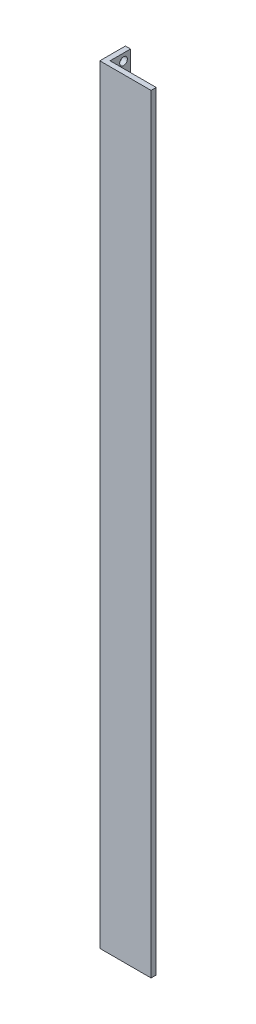
SolidWorks part; units mm, degrees
ref_plane "Front Plane" through (0, 0, 0) normal (0, 0, 1) x (1, 0, 0)
ref_plane "Top Plane" through (0, 0, 0) normal (0, 1, 0) x (1, 0, 0)
ref_plane "Right Plane" through (0, 0, 0) normal (1, 0, 0) x (0, 0, -1)
sketch "Sketch1" plane through (0, 0, 0) normal (0, 1, 0) x (1, 0, 0)
  line L0 (0, 0) -> (0, 10)
  line L1 (0, 10) -> (2, 10)
  line L2 (2, 10) -> (2, 2)
  line L3 (2, 2) -> (20, 2)
  line L4 (20, 2) -> (20, 0)
  line L5 (20, 0) -> (0, 0)
extrude "Boss-Extrude1" add sketch "Sketch1" along normal blind 300
sketch "Sketch2" plane through (0, 0, 0) normal (-1, 0, 0) x (0, 0, 1)
  circle A0 centre (-7.2626, 297.2454) radius 1.5
  circle A1 centre (-7.2585, 88.7434) radius 1.5
extrude "Cut-Extrude1" cut sketch "Sketch2" against normal through all
